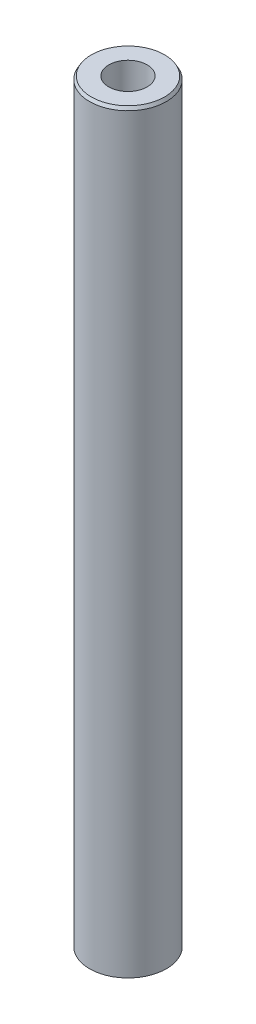
SolidWorks part; units mm, degrees
ref_plane "Front Plane" through (0, 0, 0) normal (0, 0, 1) x (1, 0, 0)
ref_plane "Top Plane" through (0, 0, 0) normal (0, 1, 0) x (1, 0, 0)
ref_plane "Right Plane" through (0, 0, 0) normal (1, 0, 0) x (0, 0, -1)
sketch "Sketch1" plane through (0, 0, 0) normal (0, 1, 0) x (1, 0, 0)
  circle A0 centre (0, 0) radius 7.5
  dimension "SHAFT_OD" = 15
extrude "Boss-Extrude1" add sketch "Sketch1" along normal blind 147.7247
sketch "Sketch2" plane through (0, 0, 0) normal (0, 1, 0) x (1, 0, 0)
  circle A0 centre (0, 0) radius 3.7477
  dimension "BORE_D" = 7.4954
extrude "Cut-Extrude1" cut sketch "Sketch2" along normal through all
chamfer "Chamfer1" distance 0.6058 angle 30 2 edges at (0, 147.7247, 7.5) (0, 0, 7.5) first distance on face at (0, 147.7247, 7.5) first distance on face at (0, 0, 3.7477)
